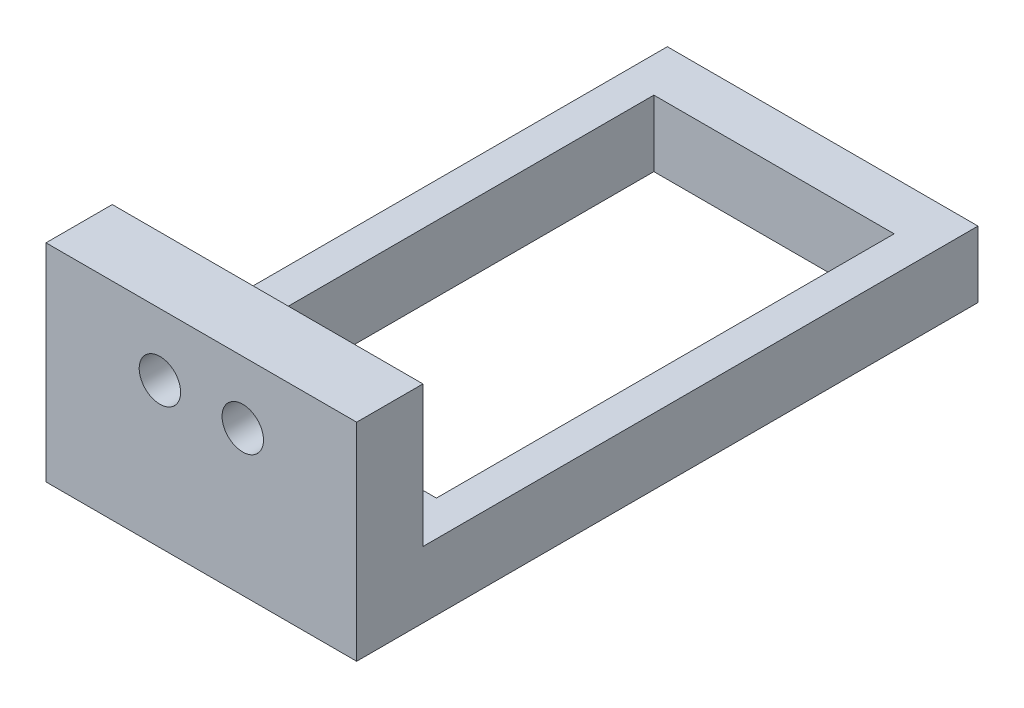
SolidWorks part; units mm, degrees
ref_plane "Front Plane" through (0, 0, 0) normal (0, 0, 1) x (1, 0, 0)
ref_plane "Top Plane" through (0, 0, 0) normal (0, 1, 0) x (1, 0, 0)
ref_plane "Right Plane" through (0, 0, 0) normal (1, 0, 0) x (0, 0, -1)
sketch "Sketch1" plane through (0, 0, 0) normal (0, 1, 0) x (1, 0, 0)
  line L1 (-7.5, 15) -> (7.5, 15)
  line L2 (-7.5, 15) -> (-7.5, -15)
  line L3 (-7.5, -15) -> (7.5, -15)
  line L4 (7.5, 15) -> (7.5, -15)
  line L5 (-7.5, 15) -> (7.5, -15) construction
  line L6 (-7.5, -15) -> (7.5, 15) construction
  point P0 (0, 0)
  dimension "D1" = 15
  dimension "D2" = 30
extrude "Boss-Extrude1" add sketch "Sketch1" along normal blind 10
sketch "Sketch4" plane through (0, 0, -15) normal (0, 0, -1) x (-1, 0, 0)
  line L0 (-7.5, 10) -> (-7.5, 0) construction
  line L1 (-7.5, 3.2) -> (7.5, 3.2)
  line L2 (-7.5, 3.2) -> (-7.5, 10)
  line L3 (-7.5, 10) -> (7.5, 10)
  line L4 (7.5, 3.2) -> (7.5, 10)
  dimension "D1" = 6.8
extrude "Cut-Extrude2" cut sketch "Sketch4" against normal blind 26.8
sketch "Sketch5" plane through (0, 0, 15) normal (0, 0, 1) x (1, 0, 0)
  line L1 (-7.5, 10) -> (7.5, 10) construction
  line L3 (-7.5, 10) -> (-7.5, 0) construction
  circle A0 centre (-2, 7) radius 1
  circle A1 centre (2, 7) radius 1
  dimension "D1" = 2
  dimension "D2" = 2
  dimension "D3" = 3
  dimension "D4" = 0
  dimension "D5" = 4
  dimension "D6" = 5.5
extrude "Cut-Extrude3" cut sketch "Sketch5" against normal through all
sketch "Sketch6" plane through (0, 3.2, 0) normal (0, 1, 0) x (1, 0, 0)
  line L1 (5.8, 12.65) -> (-5.8, 12.65)
  line L2 (5.8, 12.65) -> (5.8, -9.45)
  line L3 (5.8, -9.45) -> (-5.8, -9.45)
  line L4 (-5.8, 12.65) -> (-5.8, -9.45)
  line L5 (5.8, 12.65) -> (-5.8, -9.45) construction
  line L6 (5.8, -9.45) -> (-5.8, 12.65) construction
  line L9 (7.5, -11.8) -> (7.5, 15) construction
  line L11 (7.5, 15) -> (-7.5, 15) construction
  dimension "D1" = 11.6
  dimension "D2" = 22.1
  dimension "D3" = 1.7
  dimension "D4" = 2.35
extrude "Cut-Extrude4" cut sketch "Sketch6" against normal through all
